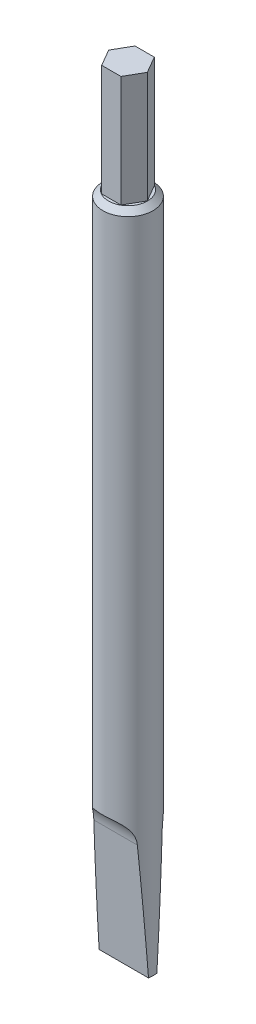
SolidWorks part; units mm, degrees
ref_plane "Front Plane" through (0, 0, 0) normal (0, 0, 1) x (1, 0, 0)
ref_plane "Top Plane" through (0, 0, 0) normal (0, 1, 0) x (1, 0, 0)
ref_plane "Right Plane" through (0, 0, 0) normal (1, 0, 0) x (0, 0, -1)
sketch "Sketch1" plane through (0, 0, 0) normal (0, 1, 0) x (1, 0, 0)
  line L1 (1.7321, 3) -> (-1.7321, 3)
  line L2 (-1.7321, 3) -> (-3.4641, 0)
  line L3 (-3.4641, 0) -> (-1.7321, -3)
  line L4 (-1.7321, -3) -> (1.7321, -3)
  line L5 (1.7321, -3) -> (3.4641, 0)
  line L6 (3.4641, 0) -> (1.7321, 3)
  circle A0 centre (0, 0) radius 4.5
  circle A1 centre (0, 0) radius 3 construction
  dimension "D1" = 9
  dimension "D2" = 6
extrude "Boss-Extrude1" add sketch "Sketch1" along normal blind 20 contours L1 L2 L3 L4 L5 L6
extrude "Boss-Extrude2" add sketch "Sketch1<3>" against normal blind 120 contours L5 L6 L1 L2 L3 L4 | A0 L6 L5 L4 L3 L2 L1 region at (0, 0, 0) region at (-4.3727, 0, 0)
sketch "Sketch1<3>" plane through (0, 0, 0) normal (0, 1, 0) x (1, 0, 0) same geometry as "Sketch1"
sketch "Sketch3" plane through (0, 0, 0) normal (1, 0, 0) x (0, 0, -1)
  line L1 (-4.5, -120) -> (4.5, -120) construction
  line L2 (4.5, -120) -> (0.75, -120)
  line L3 (-4.5, -120) -> (-4.5, -95)
  line L5 (4.5, -120) -> (4.5, 0) construction
  line L6 (4.5, -95) -> (4.5, -120)
  line L7 (0.75, -120) -> (2.229, -98.8487)
  line L8 (-0.75, -120) -> (-4.5, -120)
  line L9 (-0.75, -120) -> (-2.229, -98.8487)
  line L12 (2.4982, -95) -> (-2.4982, -95) construction
  line L13 (0, -95) -> (0, -120) construction
  arc A1 (4.5, -95) -> (2.229, -98.8487) centre (7.2169, -99.1975) ccw
  arc A2 (-4.5, -95) -> (-2.229, -98.8487) centre (-7.2169, -99.1975) cw
  dimension "D2" = 10
  dimension "D3" = 4
  dimension "D4" = 1.5
extrude "Cut-Extrude1" cut sketch "Sketch3" against normal through all both and the other way through all contours L7 L2 L6 | L8 L9 L3 region at (0, -109.1846, -3.0183) region at (0, -109.1846, 3.0183)
chamfer "Chamfer1" distance 1 angle 45 1 edges at (0, 0, 4.5)
